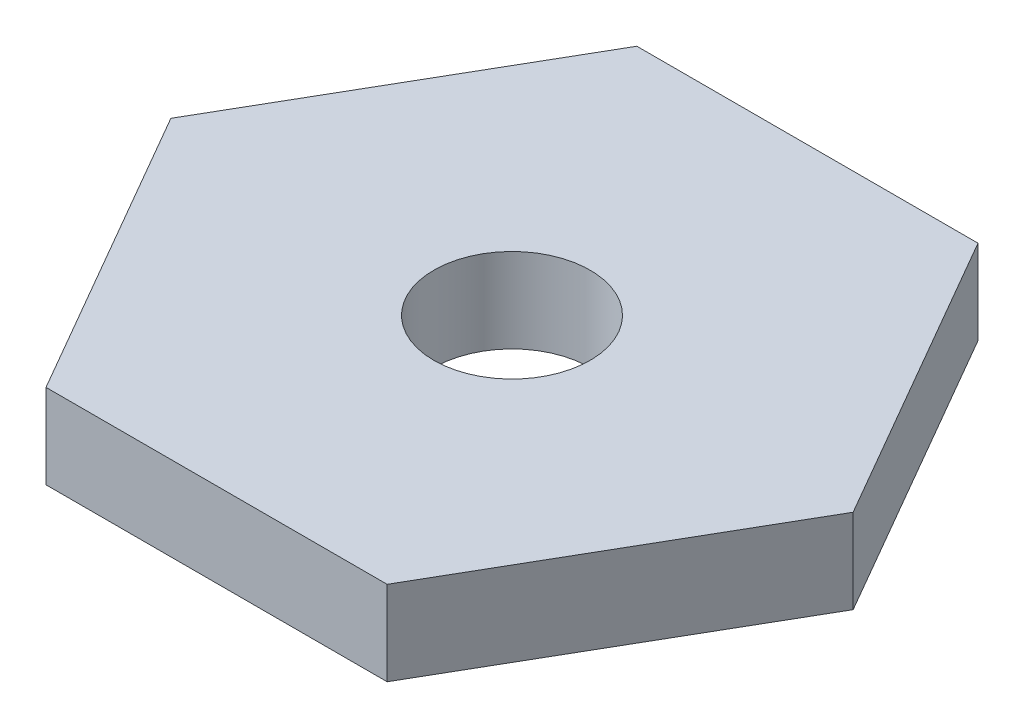
SolidWorks part; units mm, degrees
ref_plane "Plan de face" through (0, 0, 0) normal (0, 0, 1) x (1, 0, 0)
ref_plane "Plan de dessus" through (0, 0, 0) normal (0, 1, 0) x (1, 0, 0)
ref_plane "Plan de droite" through (0, 0, 0) normal (1, 0, 0) x (0, 0, -1)
sketch "Esquisse1" plane through (0, 0, 0) normal (0, 1, 0) x (1, 0, 0)
  line L1 (40.4145, 0) -> (20.2073, 35)
  line L2 (20.2073, 35) -> (-20.2073, 35)
  line L3 (-20.2073, 35) -> (-40.4145, 0)
  line L4 (-40.4145, 0) -> (-20.2073, -35)
  line L5 (-20.2073, -35) -> (20.2073, -35)
  line L6 (20.2073, -35) -> (40.4145, 0)
  circle A0 centre (0, 0) radius 35 construction
  circle A1 centre (0, 0) radius 9.2594
  dimension "D1" = 35
extrude "Boss.-Extru.1" add sketch "Esquisse1" along normal blind 10
